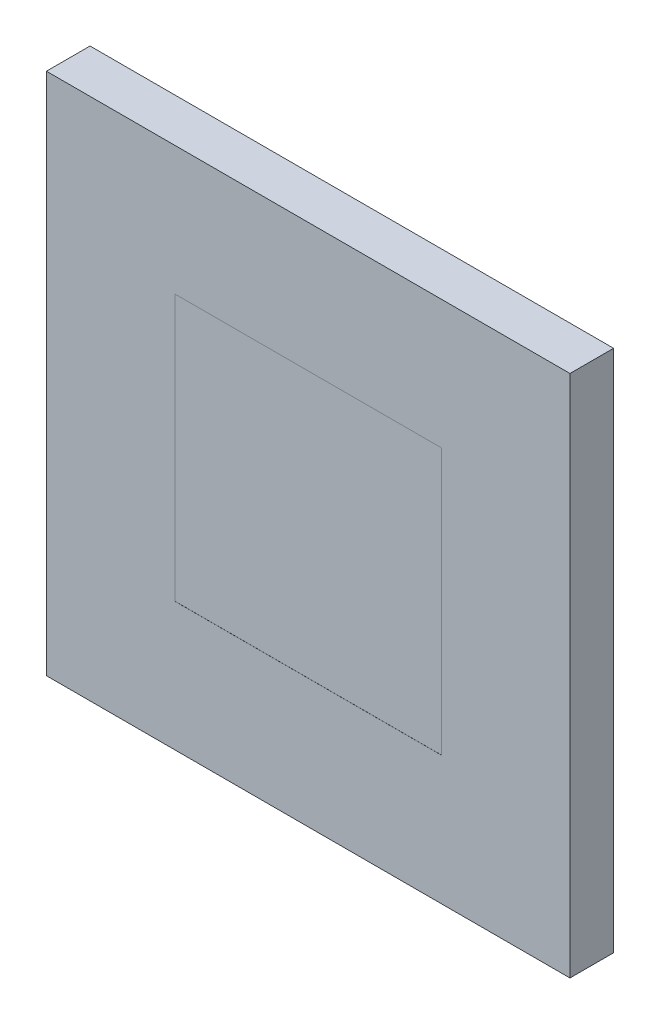
SolidWorks part; units mm, degrees
ref_plane "Front Plane" through (0, 0, 0) normal (0, 0, 1) x (1, 0, 0)
ref_plane "Top Plane" through (0, 0, 0) normal (0, 1, 0) x (1, 0, 0)
ref_plane "Right Plane" through (0, 0, 0) normal (1, 0, 0) x (0, 0, -1)
sketch "Sketch1" plane through (0, 0, 0) normal (0, 0, 1) x (1, 0, 0)
  line L1 (0, 0) -> (600, 0)
  line L2 (0, 0) -> (0, 600)
  line L3 (0, 600) -> (600, 600)
  line L4 (600, 0) -> (600, 600)
  dimension "D1" = 600
extrude "Boss-Extrude1" add sketch "Sketch1" along normal blind 50
sketch "Sketch2" plane through (0, 0, 50) normal (0, 0, 1) x (1, 0, 0)
  line L0 (0, -27.5) -> (0, 27.5) construction
  line L1 (147.5, 147.5) -> (452.5, 147.5)
  line L2 (147.5, 147.5) -> (147.5, 452.5)
  line L3 (147.5, 452.5) -> (452.5, 452.5)
  line L4 (452.5, 147.5) -> (452.5, 452.5)
  line L5 (600, 600) -> (0, 600) construction
  dimension "D1" = 305
  dimension "D2" = 147.5
  dimension "D3" = 147.5
extrude "Cut-Extrude1" cut sketch "Sketch2" against normal blind 0.1
